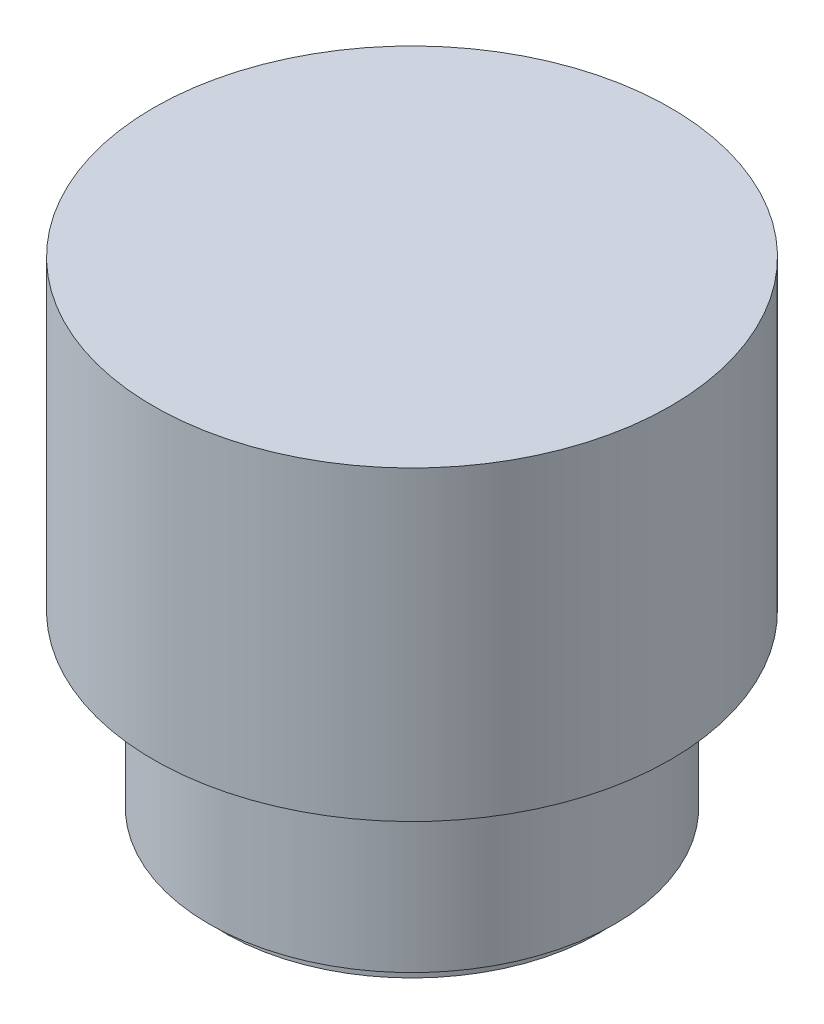
SolidWorks part; units mm, degrees
material "ABS PC"
ref_plane "Front Plane" through (0, 0, 0) normal (0, 0, 1) x (1, 0, 0)
ref_plane "Top Plane" through (0, 0, 0) normal (0, 1, 0) x (1, 0, 0)
ref_plane "Right Plane" through (0, 0, 0) normal (1, 0, 0) x (0, 0, -1)
sketch "Sketch1" plane through (0, 0, 0) normal (0, 0, 1) x (1, 0, 0)
  line L0 (0, -426.0881) -> (0, 20878.3164) construction
  line L1 (0, 0) -> (-23.5, 0)
  line L2 (-23.5, 0) -> (-23.5, 2)
  line L3 (-23.5, 2) -> (-25.5, 2)
  line L4 (-25.5, 2) -> (-25.5, 23.4)
  line L5 (-25.5, 23.4) -> (-32.5, 23.4)
  line L6 (-32.5, 23.4) -> (-32.5, 61.9)
  line L7 (-32.5, 61.9) -> (0, 61.9)
  line L8 (0, 61.9) -> (0, 0)
  dimension "D1" = 51
  dimension "D2" = 65
  dimension "D3" = 61.9
  dimension "D4" = 38.5
  dimension "D5" = 2
  dimension "D6" = 2
revolve "Revolve1" add sketch "Sketch1" angle 360 about L0
ref_plane "Plane2" through (0, 41.5, 0) normal (0, -1, 0) x (-1, 0, 0)
sketch "Sketch2" plane through (0, 41.5, 0) normal (0, -1, 0) x (-1, 0, 0)
  line L0 (-19.9299, 32.5) -> (-19.85, 14.195)
  line L1 (-19.85, 14.195) -> (-13.5, 14.195)
  line L2 (-13.5, 14.195) -> (-13.5, 32.5)
  line L3 (-13.5, 32.5) -> (-19.9299, 32.5)
  line L4 (-13.5, -985.805) -> (-13.5, 49014.195) construction
  circle A0 centre (0, 0) radius 32.5 construction
  point P2 (0, 0)
  point P10 (-19.9002, 25.695)
  dimension "D1" = 12.7
  dimension "D2" = 13.5
  dimension "D3" = 0.25
  dimension "D4" = 11.5
revolve "Cut-Revolve1" cut sketch "Sketch2" angle 360 about L4
mirror "Mirror1" about plane through (0, 0, 0) normal (1, 0, 0) of "Cut-Revolve1"
sketch "Sketch3" plane through (0, 0, 0) normal (0, -1, 0) x (1, 0, 0)
  line L1 (15, 15) -> (-15, 15) construction
  line L2 (15, 15) -> (15, -15) construction
  line L3 (15, -15) -> (-15, -15) construction
  line L4 (-15, 15) -> (-15, -15) construction
  line L5 (15, 15) -> (-15, -15) construction
  line L6 (15, -15) -> (-15, 15) construction
  circle A0 centre (-15, 15) radius 1.25
  circle A1 centre (-15, -15) radius 1.25
  circle A2 centre (15, -15) radius 1.25
  circle A3 centre (15, 15) radius 1.25
  point P0 (0, 0)
  dimension "D2" = 2.5
  dimension "D1" = 30
extrude "Cut-Extrude1" cut sketch "Sketch3" against normal blind 8
